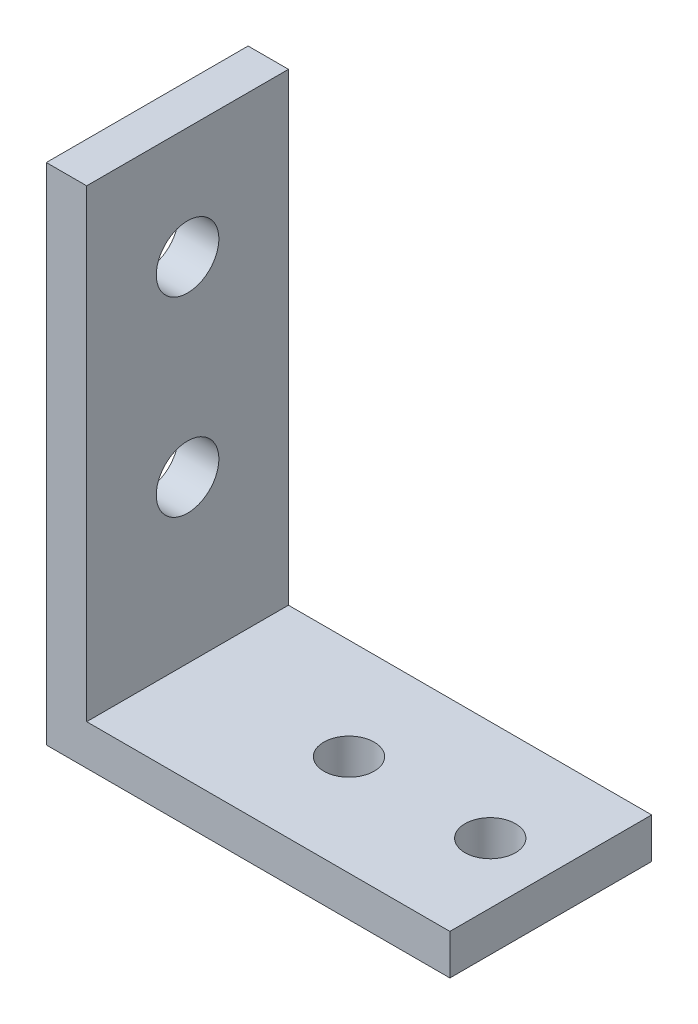
SolidWorks part; units mm, degrees
material "1060 Alloy"
ref_plane "Front Plane" through (0, 0, 0) normal (0, 0, 1) x (1, 0, 0)
ref_plane "Top Plane" through (0, 0, 0) normal (0, 1, 0) x (1, 0, 0)
ref_plane "Right Plane" through (0, 0, 0) normal (1, 0, 0) x (0, 0, -1)
sketch "Sketch1" plane through (0, 0, 0) normal (0, 0, 1) x (1, 0, 0)
  line L0 (0, 0) -> (0, 25)
  line L1 (0, 25) -> (2, 25)
  line L2 (2, 25) -> (2, 2)
  line L3 (2, 2) -> (20, 2)
  line L4 (20, 2) -> (20, 0)
  line L5 (20, 0) -> (0, 0)
  dimension "D1" = 2
  dimension "D2" = 25
  dimension "D3" = 20
extrude "Base" add sketch "Sketch1" along normal mid plane 10
hole_wizard "M3x0.5 MountHoles" positions "Sketch3" profile "Sketch4" tap size "M3x0.5" standard "ANSI Metric" end condition through all
sketch "Sketch3" plane through (0, 0, 0) normal (0, -1, 0) x (-1, 0, 0)
  line L1 (0, -5) -> (0, 5) construction
  point P0 (-10, 0)
  point P2 (-17, 0)
  dimension "D1" = 10
  dimension "D2" = 17
cosmetic thread "Hole Thread3" parameters "D2"=3
cosmetic thread "Hole Thread4" parameters "D2"=3
sketch "Sketch4" plane through (10, 0, 0) normal (1, 0, 0) x (0, 0, -1)
  line L0 (0, 0) -> (0, 25)
  line L1 (0, 25) -> (1.25, 25)
  line L2 (1.25, 25) -> (1.25, 0)
  line L5 (1.25, 0) -> (0, 0)
  line L11 (0, -6.35) -> (0, 107.95) construction
  dimension "Thru Tap Drill Dia." = 2.5
  dimension "Thru Tap Drill Depth" = 25
hole_wizard "Ø3.1 (3.1) LimitSwitchHoles" positions "3DSketch1" profile "Sketch5" hole size "Ø3.1" standard "ANSI Metric" end condition through all
sketch3d "3DSketch1"
  line L1 (0, 0, 5) -> (0, 0, -5) construction
  point P16 (0, 10, 0)
  point P18 (0, 19.45, 0)
  dimension "D1" = 10
  dimension "D2" = 19.45
sketch "Sketch5" plane through (0, 10, 0) normal (0, 1, 0) x (0, 0, 1)
  line L0 (0, 0) -> (0, 20)
  line L1 (0, 20) -> (1.55, 20)
  line L2 (1.55, 20) -> (1.55, 0)
  line L5 (1.55, 0) -> (0, 0)
  line L11 (0, -6.35) -> (0, 107.95) construction
  dimension "Thru Hole Dia." = 3.1
  dimension "Thru Hole Depth" = 20
